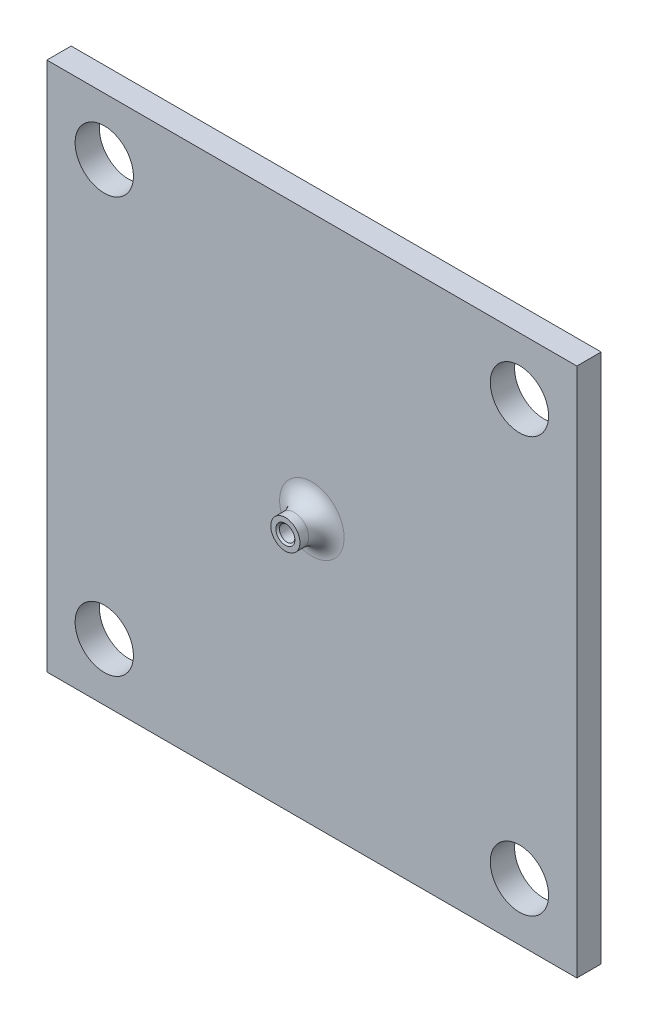
SolidWorks part; units mm, degrees
ref_plane "Piano frontale" through (0, 0, 0) normal (0, 0, 1) x (1, 0, 0)
ref_plane "Piano superiore" through (0, 0, 0) normal (0, 1, 0) x (1, 0, 0)
ref_plane "Piano destro" through (0, 0, 0) normal (1, 0, 0) x (0, 0, -1)
sketch "Sketch1" plane through (0, 0, 0) normal (0, 0, 1) x (1, 0, 0)
  line L0 (-30, 30) -> (-10, 30)
  line L1 (0, 30) -> (-10, 30)
  line L2 (30, 30) -> (30, -30)
  line L3 (30, -30) -> (10, -30)
  line L4 (-30, 30) -> (-30, -30)
  line L5 (10, -30) -> (0, -30)
  line L10 (0, 30) -> (30, 30)
  line L11 (0, -30) -> (-30, -30)
  circle A0 centre (-23.5, 23.5) radius 3.3
  circle A3 centre (-23.5, -23.5) radius 3.3
  circle A4 centre (23.5, -23.5) radius 3.3
  circle A5 centre (23.5, 23.5) radius 3.3
  point P0 (0, 0)
  dimension "D1" = 60
  dimension "D3" = 6.6
  dimension "D2" = 60
extrude "Boss-Extrude1" add sketch "Sketch1" along normal blind 0.75
sketch "Sketch2" plane through (0, 0, 0.75) normal (0, 0, 1) x (1, 0, 0)
  circle A0 centre (0, 0) radius 1
  dimension "D1" = 2
sketch "Sketch3" plane through (0, 0, 0) normal (0, 0, -1) x (-1, 0, 0)
  circle A0 centre (0, 0) radius 11.25
  dimension "D1" = 22.5
loft "Cut-Loft1" cut profiles "Sketch2", "Sketch3" connector at (0.385, 0.9229, 0.75) connector at (-2.1497, 11.0427, 0)
sketch "Sketch4" plane through (0, 0, 0) normal (0, 0, -1) x (-1, 0, 0)
  circle A0 centre (0, 0) radius 23.5
  circle A1 centre (0, 0) radius 11.25
  dimension "D1" = 47
  dimension "D2" = 22.5
extrude "Boss-Extrude2" add sketch "Sketch4" along normal blind 1
sketch "Sketch5" plane through (0, 0, 0.75) normal (0, 0, 1) x (1, 0, 0)
  circle A0 centre (0, 0) radius 0.875
  circle A1 centre (0, 0) radius 1.65
  dimension "D1" = 3.3
  dimension "D2" = 1.75
extrude "Boss-Extrude3" add sketch "Sketch5" along normal blind 5
fillet "Fillet1" radius 4 1 edges at (1.65, 0, 0.75)
fillet "Fillet2" radius 5 1 edges at (-11.25, 0, 0)
sketch "Sketch6" plane through (0, 0, -1) normal (0, 0, -1) x (-1, 0, 0)
  circle A0 centre (0, 0) radius 17.35
  circle A1 centre (0, 0) radius 19.15
  dimension "D1" = 34.7
  dimension "D2" = 38.3
extrude "Cut-Extrude1" cut sketch "Sketch6" against normal blind 1.3
sketch "Sketch7" plane through (0, 0, 0.75) normal (0, 0, 1) x (1, 0, 0)
  line L4 (-30, -30) -> (30, -30)
  line L5 (30, -30) -> (30, 30)
  line L6 (30, 30) -> (-30, 30)
  line L7 (-30, 30) -> (-30, -30)
  line L8 (-30, -30) -> (30, -30)
  line L9 (30, -30) -> (30, 30)
  line L10 (30, 30) -> (-30, 30)
  line L11 (-30, 30) -> (-30, -30)
  circle A0 centre (23.5, 23.5) radius 3.3 construction
  circle A1 centre (23.5, -23.5) radius 3.3 construction
  circle A2 centre (-23.5, 23.5) radius 3.3 construction
  circle A3 centre (-23.5, -23.5) radius 3.3 construction
  circle A4 centre (23.5, 23.5) radius 3.3
  circle A5 centre (23.5, -23.5) radius 3.3
  circle A6 centre (-23.5, 23.5) radius 3.3
  circle A7 centre (-23.5, -23.5) radius 3.3
  dimension "D1" = 0
extrude "Boss-Extrude5" add sketch "Sketch7" along normal blind 2
fillet "Fillet3" radius 2 1 edges at (-2.1859, 0, 2.75)
sketch "Sketch11" plane through (0, 0, 2.75) normal (0, 0, 1) x (1, 0, 0)
  circle A0 centre (0, 0) radius 0.75
  dimension "D1" = 1.5
extrude "Cut-Extrude2" cut sketch "Sketch11" against normal through all
chamfer "Chamfer1" distance 0.2 angle 45 1 edges at (0.875, 0, 5.75)
sketch "Sketch13" plane through (0, 0, 5.75) normal (0, 0, 1) x (1, 0, 0)
